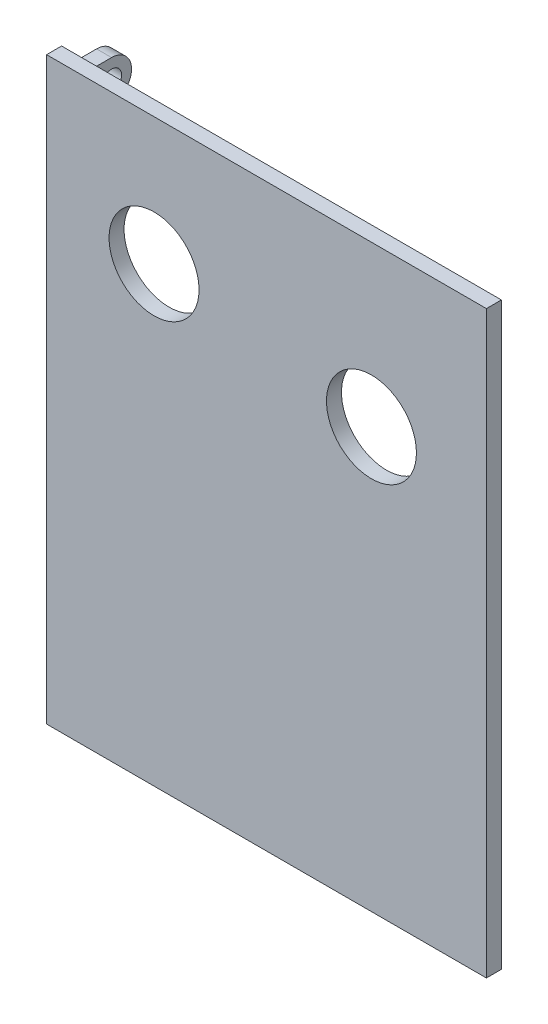
SolidWorks part; units mm, degrees
ref_plane "Front Plane" through (0, 0, 0) normal (0, 0, 1) x (1, 0, 0)
ref_plane "Top Plane" through (0, 0, 0) normal (0, 1, 0) x (1, 0, 0)
ref_plane "Right Plane" through (0, 0, 0) normal (1, 0, 0) x (0, 0, -1)
sketch "Sketch1" plane through (0, 0, 0) normal (0, 0, 1) x (1, 0, 0)
  line L1 (-44, -58) -> (44, -58)
  line L2 (-44, -58) -> (-44, 58)
  line L3 (-44, 58) -> (44, 58)
  line L4 (44, -58) -> (44, 58)
  line L5 (-44, -58) -> (44, 58) construction
  line L6 (-44, 58) -> (44, -58) construction
  circle A0 centre (-22.8181, 25.0296) radius 20 construction
  circle A1 centre (24.0245, 19.8034) radius 20 construction
  point P0 (0, 0)
  dimension "D3" = 40
  dimension "D1" = 88
  dimension "D2" = 116
extrude "Boss-Extrude1" add sketch "Sketch1" along normal blind 3 contours L3 L4 L1 L2
sketch "Sketch2" plane through (0, 0, 3) normal (0, 0, 1) x (1, 0, 0)
  line L0 (-44, -58) -> (-44, 58) construction
  line L2 (44, 0) -> (-44, 0) construction
  line L3 (44, -58) -> (44, 58) construction
  circle A0 centre (-22.5, 32.5) radius 20 construction
  circle A1 centre (21, 26) radius 20 construction
  circle A2 centre (-22.5, 32.5) radius 9
  circle A3 centre (21, 26) radius 9
  dimension "D1" = 43.5
  dimension "D2" = 40
  dimension "D3" = 23
  dimension "D6" = 18
  dimension "D4" = 26
  dimension "D5" = 32.5
extrude "Cut-Extrude1" cut sketch "Sketch2" against normal through all
sketch "Sketch4" plane through (-44, 0, 0) normal (-1, 0, 0) x (0, 0, 1)
  line L0 (0, 0) -> (10.9251, 0) construction
  line L1 (0, 58) -> (0, 50) construction
  line L2 (0, -58) -> (0, 58) construction
  line L3 (0, 50) -> (-7, 50) construction
  line L4 (-7, 54) -> (0, 54)
  line L5 (0, 54) -> (0, 46)
  line L6 (0, 46) -> (-7, 46)
  line L7 (0, -50) -> (-7, -50) construction
  line L8 (0, -58) -> (0, -50) construction
  line L9 (0, -46) -> (-7, -46)
  line L10 (0, -54) -> (0, -46)
  line L11 (-7, -54) -> (0, -54)
  circle A0 centre (-7, 50) radius 2
  arc A1 (-7, 54) -> (-7, 46) centre (-7, 50) ccw
  arc A2 (-7, -54) -> (-7, -46) centre (-7, -50) cw
  circle A3 centre (-7, -50) radius 2
  point P13 (0, 46)
  point P16 (-1.0435, 54)
  dimension "D3" = 8
  dimension "D4" = 4
  dimension "D1" = 7
  dimension "D2" = 8
extrude "Boss-Extrude3" add sketch "Sketch4" against normal blind 3
